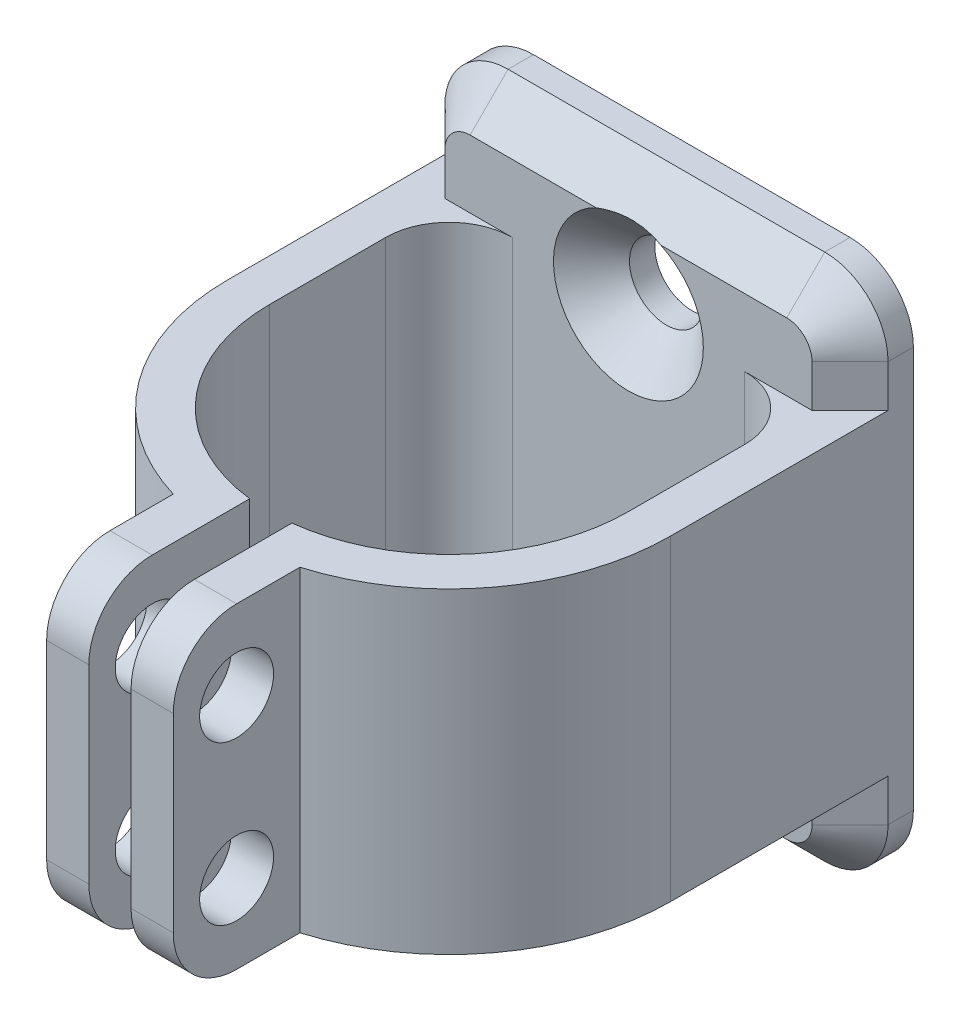
SolidWorks part; units mm, degrees
ref_plane "Front Plane" through (0, 0, 0) normal (0, 0, 1) x (1, 0, 0)
ref_plane "Top Plane" through (0, 0, 0) normal (0, 1, 0) x (1, 0, 0)
ref_plane "Right Plane" through (0, 0, 0) normal (1, 0, 0) x (0, 0, -1)
sketch "Sketch1" plane through (0, 0, 0) normal (0, 0, 1) x (1, 0, 0)
  line L1 (-10.5, 12.5) -> (10.5, 12.5)
  line L2 (-10.5, 12.5) -> (-10.5, -12.5)
  line L3 (-10.5, -12.5) -> (10.5, -12.5)
  line L4 (10.5, 12.5) -> (10.5, -12.5)
  line L5 (-10.5, 12.5) -> (10.5, -12.5) construction
  line L6 (-10.5, -12.5) -> (10.5, 12.5) construction
  line L8 (0, 7.5) -> (0, -7.5) construction
  circle A0 centre (0, 7.5) radius 1.75
  circle A3 centre (0, -7.5) radius 1.75
  point P0 (0, 0)
  point P5 (0, 0)
  point P6 (0, 0)
  dimension "D1" = 3.5
  dimension "D2" = 5
  dimension "D3" = 15
  dimension "D5" = 21
extrude "Boss-Extrude1" add sketch "Sketch1" along normal blind 3
sketch "Sketch3" plane through (0, 0, 0) normal (0, 1, 0) x (1, 0, 0)
  line L0 (10.5, -3) -> (-10.5, -3) construction
  line L10 (-8.5, -3) -> (-8.5, -11.5)
  line L25 (-27.6265, -787.8792) -> (29.8019, -2.8849) construction
  line L26 (-24.1749, -713.2878) -> (27.6541, -4.8322) construction
  line L27 (10.5004, -4.4068) -> (27.6541, -4.8322) construction
  line L28 (-10.5, -10.4105) -> (-24.1749, -713.2878) construction
  line L29 (-11.6968, 30.8925) -> (-27.6265, -787.8792) construction
  line L30 (10.5463, -2.4073) -> (29.8019, -2.8849) construction
  line L33 (-10.5, -10.4105) -> (-10.5, -10.4105) construction
  line L37 (-3, -21.5623) -> (-3, -27.5623)
  line L38 (-3, -27.5623) -> (-1, -27.5623)
  line L41 (-1, -27.5623) -> (-1, -19.941)
  line L44 (-11.6968, 30.8925) -> (-8.5, -3) construction
  line L46 (-10.5, -3) -> (-8.5, -3)
  line L48 (8.4285, -2.3627) -> (10.5463, -2.4073) construction
  line L49 (0, 0) -> (0, -27.5623) construction
  line L50 (8.4285, -2.3627) -> (0.8972, -3.0475) construction
  line L51 (8.4982, -4.3646) -> (7.7643, -4.4313) construction
  line L52 (8.4982, -4.3646) -> (10.5004, -4.4068) construction
  line L53 (10.5, 0) -> (-10.5, 0) construction
  line L54 (-10.5, -10.4105) -> (-10.5, -11.5) construction
  line L55 (-10.5, -11.5) -> (-10.5, -3)
  line L56 (10.5, -11.5) -> (10.5, -3)
  line L57 (10.5, -3) -> (8.5, -3)
  line L58 (1, -27.5623) -> (1, -19.941)
  line L59 (3, -27.5623) -> (1, -27.5623)
  line L60 (3, -21.5623) -> (3, -27.5623)
  line L61 (8.5, -3) -> (8.5, -11.5)
  arc A0 (-8.5, -11.5) -> (-1, -19.941) centre (0, -11.5) ccw
  arc A1 (-10.5, -11.5) -> (-3, -21.5623) centre (0, -11.5) ccw
  arc A3 (-10.5, -11.5) -> (7.7643, -4.4313) centre (0, -11.5) ccw construction
  arc A6 (-8.5, -11.5) -> (0.8972, -3.0475) centre (0, -11.5) ccw construction
  arc A7 (10.5, -11.5) -> (3, -21.5623) centre (0, -11.5) cw
  arc A8 (8.5, -11.5) -> (1, -19.941) centre (0, -11.5) cw
  dimension "D1" = 17
  dimension "D2" = 2
  dimension "D3" = 2
  dimension "D4" = 6
  dimension "D5" = 1
extrude "Boss-Extrude2" add sketch "Sketch3" against normal mid plane 15
sketch "Sketch4" plane through (3, 0, 0) normal (1, 0, 0) x (0, 0, -1)
  line L0 (-24.5623, 7.5) -> (-24.5623, -7.5) construction
  line L9 (-27.5623, 0) -> (-27.5623, 7.5) construction
  line L10 (-27.5623, 0) -> (-27.5623, -7.5) construction
  line L12 (-21.5623, -7.5) -> (-27.5623, -7.5) construction
  line L13 (-27.5623, 7.5) -> (-21.5623, 7.5) construction
  line L14 (-27.5623, -7.5) -> (-27.5623, 7.5) construction
  circle A0 centre (-24.5623, 3.75) radius 1.75
  circle A1 centre (-24.5623, -3.75) radius 1.75
  point P23 (-27.5623, 3.75)
  point P28 (-27.5623, -3.75)
  dimension "D1" = 3.5
  dimension "D2" = 3.5
extrude "Cut-Extrude1" cut sketch "Sketch4" against normal through all both and the other way through all
fillet "Fillet1" radius 3 8 edges at (-10.5, 12.5, 1.5) (-10.5, -12.5, 1.5) (10.5, -12.5, 1.5) (10.5, 12.5, 1.5) (2, -7.5, 27.5623) (-2, -7.5, 27.5623) (-2, 7.5, 27.5623) (2, 7.5, 27.5623)
fillet "Fillet3" radius 3 2 edges at (8.5, 0, 3) (-8.5, 0, 3)
chamfer "Chamfer1" distance 1.8 angle 45 12 edges at (1.75, -7.5, 3) (1.75, 7.5, 3) (-10.5, -8.5, 3) (10.5, -8.5, 3) (-9.6213, -11.6213, 3) (9.6213, -11.6213, 3) (0, -12.5, 3) (10.5, 8.5, 3) (-10.5, 8.5, 3) (9.6213, 11.6213, 3) (-9.6213, 11.6213, 3) (0, 12.5, 3)
